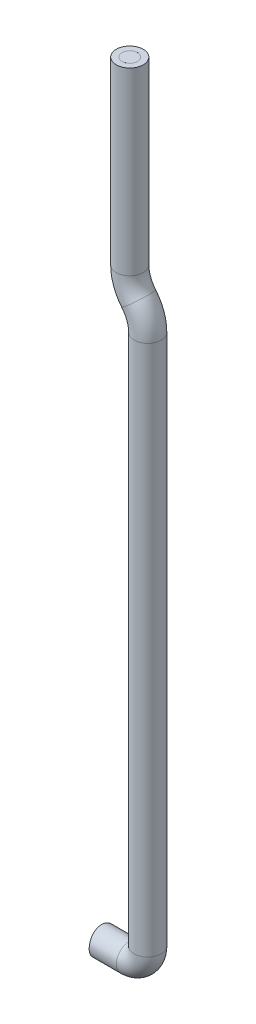
SolidWorks part; units mm, degrees
material "Изоляция провода синяя"
ref_plane "Спереди" through (0, 0, 0) normal (0, 0, 1) x (1, 0, 0)
ref_plane "Сверху" through (0, 0, 0) normal (0, 1, 0) x (1, 0, 0)
ref_plane "Справа" through (0, 0, 0) normal (1, 0, 0) x (0, 0, -1)
sketch "Эскиз1" plane through (0, 0, 0) normal (0, 1, 0) x (1, 0, 0)
  circle A0 centre (0, 0) radius 1.05
  dimension "D1" = 2.1
sketch "Эскиз2" plane through (0, 0, 0) normal (0, 0, 1) x (1, 0, 0)
  line L0 (0, 0) -> (0, 50000) construction
  line L1 (1.05, 0) -> (-1.05, 0) construction
  line L2 (-3.6, 0.6487) -> (-3.6, 50000.6487) construction
  line L3 (0, 0) -> (0, 41.3477)
  line L4 (-1.4, 59.2) -> (-1.4, 45.2)
  line L6 (-6.1, 36.9798) -> (-6.1, 50036.9798) construction
  arc A0 (-1.4, 45.2) -> (-0.7, 43.2739) centre (1.6, 45.2) ccw
  arc A1 (0, 41.3477) -> (-0.7, 43.2739) centre (-3, 41.3477) ccw
  point P4 (0, 0)
  point P16 (0, 0)
  point P18 (0, 0)
  point P19 (0, 58.3163)
  point P20 (0, 0)
  point P21 (0, 61.104)
  dimension "D5" = 14
  dimension "D3" = 3
  dimension "D1" = 3.6
  dimension "D2" = 1.4
  dimension "D4" = 41.3477
  dimension "D6" = 2.5
sweep "По траектории1" add profiles "Эскиз1" path "Эскиз2"
sketch "Эскиз3" plane through (0, 0, 0) normal (0, -1, 0) x (1, 0, 0)
  circle A0 centre (0, 0) radius 0.6
  dimension "D1" = 1.2
sweep "Вырез-По траектории1" cut profiles "Эскиз3" path "Эскиз2<2>"
sketch "Эскиз2<2>" plane through (0, 0, 0) normal (0, 0, 1) x (1, 0, 0) same geometry as "Эскиз2"
sketch "Эскиз4" plane through (0, 0, 0) normal (0, -1, 0) x (1, 0, 0)
  circle A2 centre (0, 0) radius 0.6 construction
  circle A3 centre (0, 0) radius 0.6
sweep "По траектории2" add profiles "Эскиз4" path "Эскиз2<3>"
sketch "Эскиз2<3>" plane through (0, 0, 0) normal (0, 0, 1) x (1, 0, 0) same geometry as "Эскиз2"
sketch "Эскиз5" plane through (0, 0, 0) normal (0, 0, 1) x (1, 0, 0)
  line L0 (0, 0) -> (0, -50000) construction
  line L1 (0, -1.4) -> (-50000, -1.4) construction
  line L2 (-1.05, 0) -> (1.05, 0) construction
  line L3 (-1.4, -1.4) -> (-3.6, -1.4)
  arc A0 (0, 0) -> (-1.4, -1.4) centre (-1.4, 0) cw
  dimension "D1" = 1.4
  dimension "D2" = 3.6
sketch "Эскиз6" plane through (0, 0, 0) normal (0, -1, 0) x (1, 0, 0)
  circle A1 centre (0, 0) radius 0.6
  circle A3 centre (0, 0) radius 0.6
  dimension "D1" = 0
sweep "По траектории3" add profiles "Эскиз6" path "Эскиз5"
sketch "Эскиз7" plane through (0, 0, 0) normal (0, -1, 0) x (1, 0, 0)
  circle A0 centre (0, 0) radius 0.6 construction
  circle A1 centre (0, 0) radius 1.05
  circle A2 centre (0, 0) radius 1.05
  circle A3 centre (0, 0) radius 0.6
  dimension "D1" = 0
sweep "По траектории4" add profiles "Эскиз7" path "Эскиз5<2>"
sketch "Эскиз5<2>" plane through (0, 0, 0) normal (0, 0, 1) x (1, 0, 0) same geometry as "Эскиз5"
ref_plane "Плоскость1" through (0, -2.45, 0) normal (0, -1, 0) x (-1, 0, 0)
sketch "Эскиз8" plane through (0, -2.45, 0) normal (0, -1, 0) x (-1, 0, 0)
  line L0 (3.6, -1.05) -> (3.6, 1.05) construction
  line L1 (3.6, -1.05) -> (3.6, 1.05)
  line L2 (0, 0) -> (-50000, 0) construction
  line L3 (3.6, 1.05) -> (3.5074, 1.05)
  line L5 (3.6, -1.05) -> (3.5074, -1.05)
  arc A0 (3.5074, -1.05) -> (3.5074, 1.05) centre (-2.4, 0) ccw
  dimension "D1" = 12
extrude "Вырез-Вытянуть1" cut sketch "Эскиз8" against normal blind 10 contours A0 L1 L3 region at (-3.5723, -2.45, -0.7879)
extrude "Вырез-Вытянуть2" cut sketch "Эскиз8<3>" against normal blind 10 contours A0 L5 L1 region at (-3.5723, -2.45, 0.7879)
sketch "Эскиз8<3>" plane through (0, -2.45, 0) normal (0, -1, 0) x (-1, 0, 0) same geometry as "Эскиз8"
